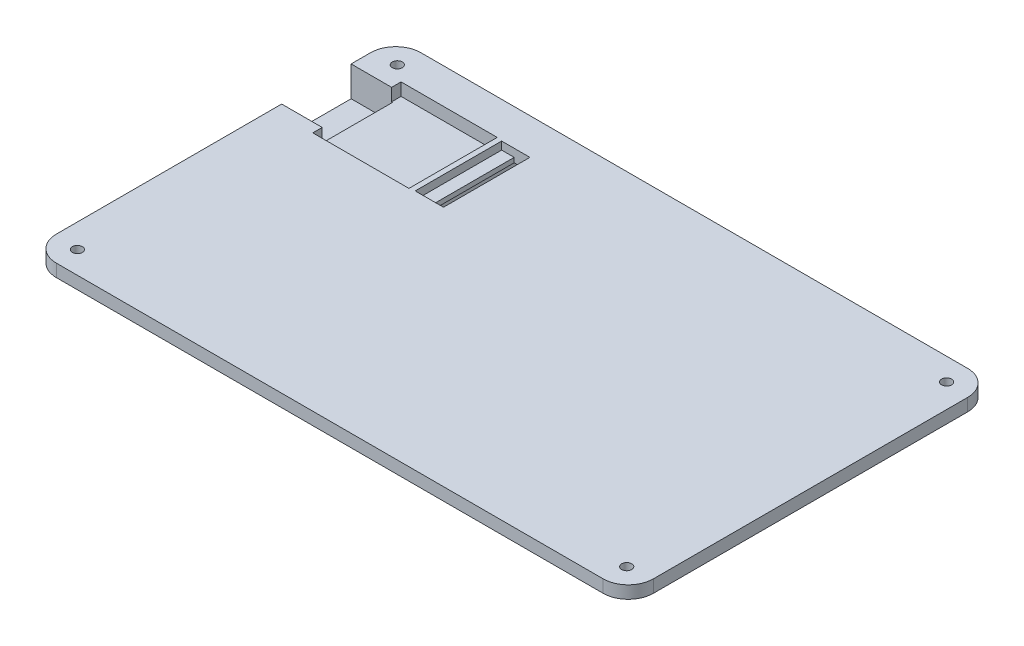
SolidWorks part; units mm, degrees
ref_plane "前视基准面" through (0, 0, 0) normal (0, 0, 1) x (1, 0, 0)
ref_plane "上视基准面" through (0, 0, 0) normal (0, 1, 0) x (1, 0, 0)
ref_plane "右视基准面" through (0, 0, 0) normal (1, 0, 0) x (0, 0, -1)
other "Configuration Table"
sketch "草图1" plane through (0, 0, 0) normal (0, 1, 0) x (1, 0, 0)
  line L1 (-136.2665, -68.2938) -> (136.2665, -68.2938)
  line L2 (-136.2665, -68.2938) -> (-136.2665, 68.2938)
  line L3 (-136.2665, 68.2938) -> (136.2665, 68.2938)
  line L4 (136.2665, -68.2938) -> (136.2665, 68.2938)
  line L5 (-136.2665, -68.2938) -> (136.2665, 68.2938) construction
  line L6 (-136.2665, 68.2938) -> (136.2665, -68.2938) construction
  point P0 (0, 0)
extrude "凸台-拉伸1" add sketch "草图1" along normal blind 4
sketch "草图2" plane through (0, 4, 0) normal (0, 1, 0) x (1, 0, 0)
  line L4 (-87, 58) -> (87, 58) construction
  line L5 (-87, 58) -> (87, 58)
  line L6 (-95, 50) -> (-95, -50)
  line L7 (-87, -58) -> (87, -58)
  line L8 (95, 50) -> (95, -50)
  line L9 (-95, -50) -> (-95, 50) construction
  line L10 (-87, -58) -> (87, -58) construction
  line L11 (95, -50) -> (95, 50) construction
  line L13 (-136.2665, 68.2938) -> (136.2665, 68.2938)
  line L14 (-136.2665, 68.2938) -> (-136.2665, -68.2938)
  line L15 (-136.2665, -68.2938) -> (136.2665, -68.2938)
  line L16 (136.2665, 68.2938) -> (136.2665, -68.2938)
  arc A0 (87, 58) -> (95, 50) centre (87, 50) cw
  arc A1 (-95, -50) -> (-87, -58) centre (-87, -50) ccw
  arc A2 (87, -58) -> (95, -50) centre (87, -50) ccw
  arc A3 (-87, 58) -> (-95, 50) centre (-87, 50) ccw
  dimension "D1" = 8
extrude "切除-拉伸1" cut sketch "草图2" against normal blind 4
sketch "草图3" plane through (0, 0, 0) normal (0, -1, 0) x (1, 0, 0)
  line L0 (-95, -22) -> (-81.8, -22)
  line L1 (-81.8, -22) -> (-81.8, -19)
  line L2 (-81.8, -19) -> (-51.8, -19)
  line L3 (-51.8, -19) -> (-81.8, -19) construction
  line L4 (-51.8, -19) -> (-51.8, -46.5)
  line L5 (-51.8, -46.5) -> (-51.8, -19) construction
  line L6 (-51.8, -46.5) -> (-81.8, -46.5)
  line L7 (-81.8, -46.5) -> (-81.8, -43.5)
  line L8 (-81.8, -43.5) -> (-81.8, -46.5) construction
  line L9 (-81.8, -43.5) -> (-81.8, -22) construction
  line L10 (-81.8, -43.5) -> (-95, -43.5)
  line L11 (-95, -43.5) -> (-95, -22)
extrude "切除-拉伸2" cut sketch "草图3" against normal blind 4
sketch "草图4" plane through (0, 0, 0) normal (0, -1, 0) x (1, 0, 0)
  line L0 (-95, -32.75) -> (-24.4506, -32.75) construction
  line L1 (-95, -43.5) -> (-95, -22) construction
  line L2 (-51.5, -18.7) -> (-51.5, -46.8)
  line L3 (-95, -21.7) -> (-95, -43.8)
  line L4 (-95, -22) -> (-81.8, -22) construction
  line L5 (-81.8, -22) -> (-81.8, -19) construction
  line L6 (-81.8, -19) -> (-51.8, -19) construction
  line L7 (-51.8, -19) -> (-51.8, -46.5) construction
  line L8 (-82.1, -46.8) -> (-51.5, -46.8)
  line L9 (-82.1, -43.8) -> (-82.1, -46.8)
  line L10 (-95, -43.8) -> (-82.1, -43.8)
  line L25 (-95, -21.7) -> (-82.1, -21.7)
  line L26 (-95, -22) -> (-95, 50) construction
  line L27 (-82.1, -21.7) -> (-82.1, -18.7)
  line L28 (-82.1, -18.7) -> (-51.5, -18.7)
  point P19 (-51.5, -32.75)
  dimension "D1" = 0.3
  dimension "D2" = 0.3
  dimension "D3" = 0.3
  dimension "D4" = 0.3
extrude "切除-拉伸3" cut sketch "草图4" against normal blind 4 contours L28 L2 L8 L9 L10 L3 L25 L27
sketch "草图5" plane through (0, 0, 0) normal (0, -1, 0) x (1, 0, 0)
  line L0 (-81.8, -43.5) -> (-81.8, -22) construction
  line L1 (-47.8, -50.75) -> (-81.8, -50.75)
  line L2 (-47.8, -50.75) -> (-47.8, -14.75)
  line L3 (-47.8, -14.75) -> (-81.8, -14.75)
  line L4 (-81.8, -50.75) -> (-81.8, -14.75)
  line L5 (-47.8, -50.75) -> (-81.8, -14.75) construction
  line L6 (-47.8, -14.75) -> (-81.8, -50.75) construction
  line L7 (-95, -32.75) -> (-25.646, -32.75) construction
  line L8 (-95, -22) -> (-95, -43.5) construction
  line L9 (-51.8, -46.5) -> (-51.8, -19) construction
  point P0 (-64.8, -32.75)
  dimension "D1" = 36
  dimension "D2" = 4
extrude "凸台-拉伸2" add sketch "草图5" along normal blind 4 contours L3 L4 L1 L2
sketch "草图6" plane through (0, 0, 0) normal (0, -1, 0) x (1, 0, 0)
  line L0 (-81.8, -18.7) -> (-81.8, -14.75) construction
  line L9 (-95, -21.7) -> (-81.8, -21.7)
  line L10 (-95, -21.7) -> (-95, -17.7)
  line L11 (-95, -17.7) -> (-81.8, -17.7)
  line L12 (-81.8, -21.7) -> (-81.8, -17.7)
  line L13 (-81.8, -50.75) -> (-81.8, -46.8) construction
  line L14 (-95, -43.8) -> (-81.8, -43.8)
  line L15 (-95, -43.8) -> (-95, -47.8)
  line L16 (-95, -47.8) -> (-81.8, -47.8)
  line L17 (-81.8, -43.8) -> (-81.8, -47.8)
  dimension "D1" = 4
  dimension "D2" = 4
extrude "凸台-拉伸3" add sketch "草图6" along normal blind 5.6
sketch "草图7" plane through (0, -5.6, 0) normal (0, -1, 0) x (1, 0, 0)
  line L0 (-95, -47.8) -> (-81.8, -47.8) construction
  line L5 (-95, -17.7) -> (-77.8, -17.7)
  line L6 (-95, -17.7) -> (-95, -47.8)
  line L7 (-95, -47.8) -> (-77.8, -47.8)
  line L8 (-77.8, -17.7) -> (-77.8, -47.8)
  line L9 (-81.8, -43.5) -> (-81.8, -22) construction
  dimension "D1" = 4
extrude "凸台-拉伸4" add sketch "草图7" along normal blind 4
sketch "草图8" plane through (0, 4, 0) normal (0, 1, 0) x (1, 0, 0)
  line L1 (-81.8, 19) -> (-45.8, 19) construction
  line L2 (-45.8, 46.5) -> (-40.8, 46.5)
  line L3 (-45.8, 46.5) -> (-45.8, 19)
  line L4 (-45.8, 19) -> (-40.8, 19)
  line L5 (-40.8, 46.5) -> (-40.8, 19)
  dimension "D1" = 5
extrude "切除-拉伸4" cut sketch "草图8" against normal blind 4
sketch "草图9" plane through (-45.8, 0, 0) normal (1, 0, 0) x (0, 0, -1)
  line L0 (19, -0.1) -> (19, 6.4) construction
  line L1 (19, 4) -> (46.5, 4)
  line L2 (19, 4) -> (19, 1.5)
  line L3 (19, 1.5) -> (46.5, 1.5)
  line L4 (46.5, 4) -> (46.5, 1.5)
  line L5 (7.5, 4) -> (21.5, 4) construction
  line L6 (46.5, 6.4) -> (46.5, 7.9) construction
  dimension "D1" = 2.5
extrude "切除-拉伸5" cut sketch "草图9" against normal blind 4
sketch "草图10" plane through (0, 4, 0) normal (0, 1, 0) x (1, 0, 0)
  circle A0 centre (87.4, 50.9) radius 1.6
  circle A1 centre (-87.4, 50.9) radius 1.6
  circle A2 centre (-87.4, -50.9) radius 1.6
  circle A3 centre (87.4, -50.9) radius 1.6
extrude "切除-拉伸6" cut sketch "草图10" against normal blind 10
